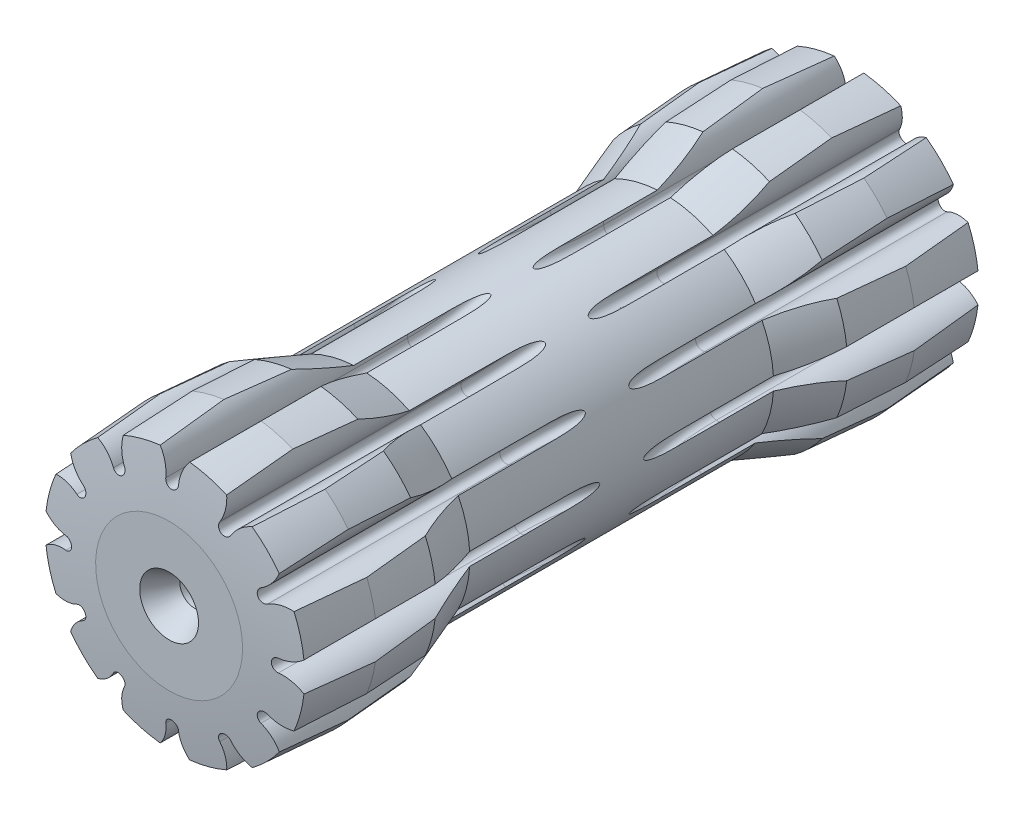
SolidWorks part; units mm, degrees
ref_plane "Front Plane" through (0, 0, 0) normal (0, 0, 1) x (1, 0, 0)
ref_plane "Top Plane" through (0, 0, 0) normal (0, 1, 0) x (1, 0, 0)
ref_plane "Right Plane" through (0, 0, 0) normal (1, 0, 0) x (0, 0, -1)
sketch "Sketch1" plane through (0, 0, 0) normal (1, 0, 0) x (0, 0, -1)
  line L0 (0, 0) -> (118.4245, 0) construction
  line L1 (0.6001, 13.25) -> (7.5, 13.69)
  line L2 (7.5, 13.69) -> (14, 13.25)
  line L3 (19.5, 11.2) -> (50.5, 11.2)
  line L4 (50.5, 11.2) -> (56, 13.25)
  line L5 (56, 13.25) -> (62.5, 13.69)
  line L6 (70, 0) -> (70, 7.5)
  line L7 (0, 0) -> (0, 7.5)
  line L8 (0, 0) -> (70, 0)
  line L9 (14, 13.25) -> (19.5, 11.2)
  line L11 (62.5, 13.69) -> (69.3999, 13.25)
  arc A0 (0, 7.5) -> (0.6001, 13.25) centre (99.7184, 0) cw
  arc A1 (70, 7.5) -> (69.3999, 13.25) centre (-29.7184, 0) ccw
  dimension "D7" = 100
  dimension "D8" = 15
  dimension "D10" = 100
  dimension "D12" = 14
  dimension "D2" = 7.5
  dimension "D3" = 14
  dimension "D4" = 7.5
  dimension "D5" = 19.5
  dimension "D6" = 22.4
  dimension "D9" = 70
  dimension "D11" = 15
  dimension "D13" = 27.38
  dimension "D14" = 19.5
  dimension "D15" = 26.5
revolve "Revolve1" add sketch "Sketch1" angle 360 about L0
sketch "Sketch2" plane through (0, 0, 0) normal (1, 0, 0) x (0, 0, -1)
  line L0 (70, 3) -> (67.4019, 1.5)
  line L1 (67.4019, 1.5) -> (64.9013, 1.5)
  line L2 (64.9013, 1.5) -> (64, 0)
  line L3 (0, 0) -> (41.5, 0) construction
  line L4 (70, -7.5) -> (70, 7.5) construction
  line L5 (70, 3) -> (70, 0)
  line L6 (64, 0) -> (70, 0)
  dimension "D1" = 3
  dimension "D2" = 30
  dimension "D3" = 59
  dimension "D4" = 6
  dimension "D5" = 6
revolve "Cut-Revolve1" cut sketch "Sketch2" angle 360 about L3
sketch "Sketch3" plane through (0, 0, 0) normal (1, 0, 0) x (0, 0, -1)
  line L0 (0, 3) -> (2.5981, 1.5)
  line L1 (2.5981, 1.5) -> (5.0987, 1.5)
  line L2 (5.0987, 1.5) -> (6, 0)
  line L3 (0, 3) -> (0, 0)
  line L4 (0, 0) -> (12.7492, 0) construction
  line L5 (6, 0) -> (0, 0)
  dimension "D1" = 6
  dimension "D2" = 30
  dimension "D3" = 59
  dimension "D4" = 3
  dimension "D5" = 6
revolve "Cut-Revolve2" cut sketch "Sketch3" angle 360 about L4
ref_plane "Plane1" through (0, 0, -70) normal (0, 0, 1) x (1, 0, 0)
sketch "Sketch4" plane through (0, 0, -70) normal (0, 0, 1) x (1, 0, 0)
  line L0 (0, 0) -> (-15.7466, 0) construction
  line L1 (0, 0) -> (0, 14.7663) construction
  arc A0 (-0.65, 10.85) -> (0.65, 10.85) centre (0, 10.85) ccw
  arc A2 (1.9, 13.5575) -> (-1.9, 13.5575) centre (0, 0) ccw
  arc A3 (-1.9, 13.5575) -> (-0.65, 10.85) centre (-4.2072, 10.85) cw
  arc A4 (1.9, 13.5575) -> (0.65, 10.85) centre (4.2072, 10.85) ccw
  circle A5 centre (0, 0) radius 13.69 construction
  dimension "D1" = 1.3
  dimension "D3" = 20.4
  dimension "D2" = 3.8
extrude "Cut-Extrude1" cut sketch "Sketch4" along normal blind 25
sketch "Sketch6" plane through (0, 0, -45) normal (0, 0, -1) x (-1, 0, 0)
  line L0 (-1.5057, 13.1642) -> (-1.5057, 15.404)
  line L1 (-1.5057, 15.404) -> (1.5057, 15.404)
  line L2 (1.5057, 15.404) -> (1.5057, 13.1642)
  line L3 (-8.4949, 40.85) -> (13.6472, 40.85) construction
  arc A0 (-0.65, 10.85) -> (-1.5057, 13.1642) centre (-4.2072, 10.85) ccw construction
  arc A1 (-0.65, 10.85) -> (0.65, 10.85) centre (0, 10.85) ccw construction
  arc A2 (1.5057, 13.1642) -> (0.65, 10.85) centre (4.2072, 10.85) ccw construction
  arc A3 (-0.65, 10.85) -> (-1.5057, 13.1642) centre (-4.2072, 10.85) ccw
  arc A4 (-0.65, 10.85) -> (0.65, 10.85) centre (0, 10.85) ccw
  arc A5 (1.5057, 13.1642) -> (0.65, 10.85) centre (4.2072, 10.85) ccw
  dimension "D1" = 30
revolve "Cut-Revolve3" cut sketch "Sketch6" angle 360 about L3
ref_axis "Axis1" through (0, 0, -50.5) along (0, 0, 1)
pattern_circular "CirPattern1" count 12 over 360 about axis through (0, 0, -50.5) along (0, 0, 1) of "Cut-Extrude1", "Cut-Revolve3"
sketch "Sketch5" plane through (0, 0, 0) normal (0, 0, 1) x (1, 0, 0)
  line L0 (0, 0) -> (20.7288, 0) construction
  line L1 (0, 0) -> (0, 13.7027) construction
  line L2 (-3, 14.1961) -> (-3, 15.1961)
  line L3 (-3, 15.1961) -> (3, 15.1961)
  line L4 (3, 14.1961) -> (3, 15.1961)
  arc A2 (-0.65, 10.85) -> (0.65, 10.85) centre (0, 10.85) ccw
  arc A3 (3, 14.1961) -> (0.65, 10.85) centre (4.2072, 10.85) ccw
  arc A4 (-3, 14.1961) -> (-0.65, 10.85) centre (-4.2072, 10.85) cw
  arc A5 (-0.65, 10.85) -> (0.65, 10.85) centre (0, 10.85) ccw construction
  arc A6 (-0.65, 10.85) -> (-1.5057, 13.1642) centre (-4.2072, 10.85) ccw construction
  dimension "D1" = 6
extrude "Cut-Extrude2" cut sketch "Sketch5" against normal blind 25
sketch "Sketch8" plane through (0, 0, -25) normal (0, 0, 1) x (1, 0, 0)
  line L0 (-13.6472, 40.85) -> (11.7246, 40.85) construction
  line L1 (1.5057, 13.1642) -> (1.5057, 15.404) construction
  line L2 (1.5057, 15.404) -> (-1.5057, 15.404) construction
  line L3 (-1.5057, 15.404) -> (-1.5057, 13.1642) construction
  line L4 (1.5057, 13.1642) -> (1.5057, 15.404)
  line L5 (1.5057, 15.404) -> (-1.5057, 15.404)
  line L6 (-1.5057, 15.404) -> (-1.5057, 13.1642)
  arc A0 (-0.65, 10.85) -> (-1.5057, 13.1642) centre (-4.2072, 10.85) ccw construction
  arc A1 (1.5057, 13.1642) -> (0.65, 10.85) centre (4.2072, 10.85) ccw construction
  arc A2 (-0.65, 10.85) -> (0.65, 10.85) centre (0, 10.85) ccw construction
  arc A3 (-0.65, 10.85) -> (-1.5057, 13.1642) centre (-4.2072, 10.85) ccw
  arc A4 (1.5057, 13.1642) -> (0.65, 10.85) centre (4.2072, 10.85) ccw
  arc A5 (-0.65, 10.85) -> (0.65, 10.85) centre (0, 10.85) ccw
revolve "Cut-Revolve5" cut sketch "Sketch8" angle 360 about L0
pattern_circular "CirPattern2" count 12 over 360 about axis through (0, 0, -50.5) along (0, 0, 1) of "Cut-Extrude2", "Cut-Revolve5"
